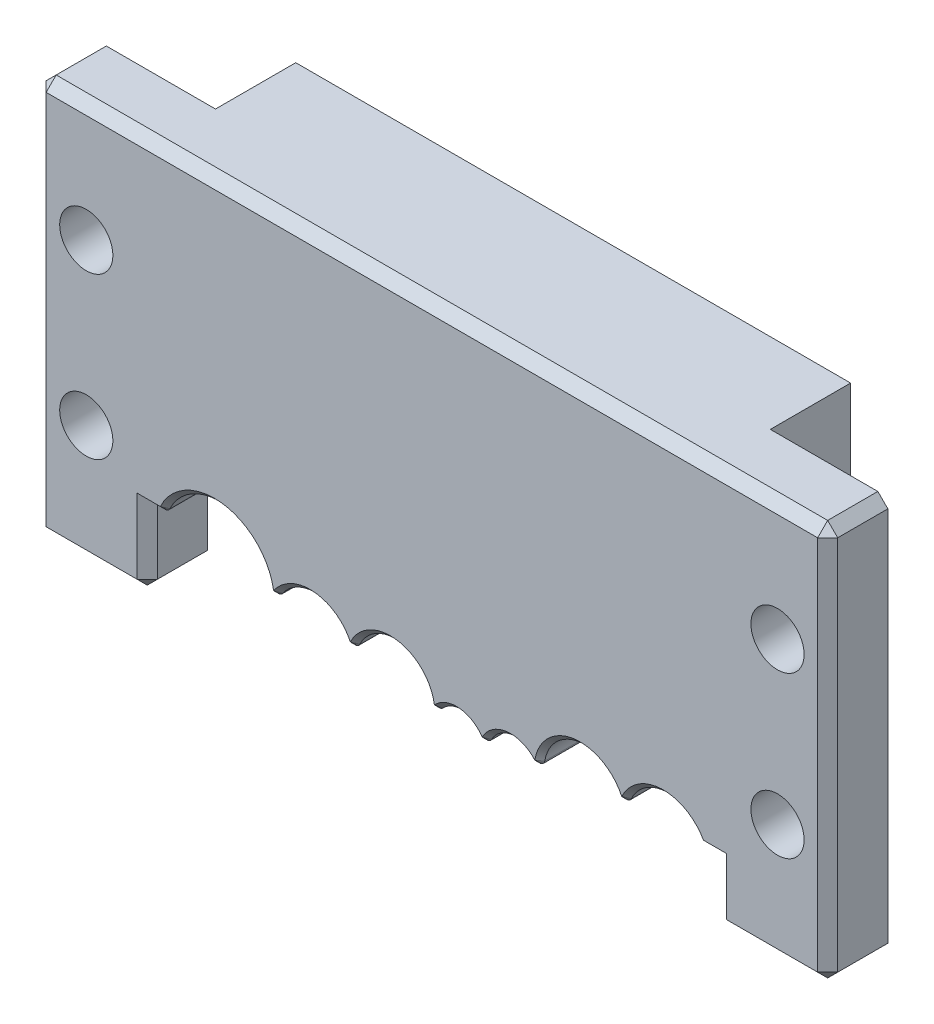
SolidWorks part; units mm, degrees
ref_plane "Front Plane" through (0, 0, 0) normal (0, 0, 1) x (1, 0, 0)
ref_plane "Top Plane" through (0, 0, 0) normal (0, 1, 0) x (1, 0, 0)
ref_plane "Right Plane" through (0, 0, 0) normal (1, 0, 0) x (0, 0, -1)
sketch "Sketch1" plane through (0, 0, 0) normal (0, 1, 0) x (1, 0, 0)
  point P0 (0, 0)
  line B0 (28.37, 45.6802) -> (28.37, 0) construction
  line B1 (28.37, 0) -> (39.45, 0) construction
  line B2 (39.45, 0) -> (39.45, 39.05) construction
  line B3 (39.45, 39.05) -> (36.7, 40.8) construction
  line B4 (36.7, 40.8) -> (36.7, 59.75) construction
  line B5 (36.7, 59.75) -> (32.77, 59.75) construction
  line B6 (32.77, 59.75) -> (32.77, 45.6802) construction
  line B7 (32.77, 45.6802) -> (28.37, 45.6802) construction
  line B8 (-28.37, 0) -> (-28.37, 45.6802) construction
  line B9 (-28.37, 45.6802) -> (-32.77, 45.6802) construction
  line B10 (-32.77, 45.6802) -> (-32.77, 59.75) construction
  line B11 (-32.77, 59.75) -> (-36.7, 59.75) construction
  line B12 (-36.7, 59.75) -> (-36.7, 40.8) construction
  line B13 (-36.7, 40.8) -> (-39.45, 39.05) construction
  line B14 (-39.45, 39.05) -> (-39.45, 0) construction
  line B15 (-39.45, 0) -> (-28.37, 0) construction
  line B16 (28.37, 0) -> (-28.37, 0) construction
  circle B17 centre (34.45, 9.5) radius 2.95 construction
  circle B18 centre (34.45, 25.5) radius 2.95 construction
  circle B19 centre (-34.45, 9.5) radius 2.95 construction
  circle B20 centre (-34.45, 25.5) radius 2.95 construction
sketch_block_instance "Block1-1"
sketch_block "Block1"
sketch "Sketch2" plane through (0, 0, 0) normal (0, 0, 1) x (1, 0, 0)
  line B0 (-39.5328, 0) -> (-39.5328, -39.5) construction
  line B1 (-39.5328, -39.5) -> (-28.4528, -39.5) construction
  line B2 (-28.4528, -39.5) -> (-28.4528, 0) construction
  line B3 (-28.4528, 0) -> (-39.5328, 0) construction
  line B4 (39.3672, -39.5) -> (39.3672, 0) construction
  line B5 (39.3672, 0) -> (28.2872, 0) construction
  line B6 (28.2872, 0) -> (28.2872, -39.5) construction
  line B7 (28.2872, -39.5) -> (39.3672, -39.5) construction
  circle B8 centre (-34.5328, -11.75) radius 2.95 construction
  circle B9 centre (34.3672, -11.75) radius 2.95 construction
  circle B10 centre (-34.5328, -27.75) radius 2.95 construction
  circle B11 centre (34.3672, -27.75) radius 2.95 construction
sketch_block_instance "Block2-1"
sketch_block "Block2"
ref_plane "Plane1" through (0, -39.5, 0) normal (0, 1, 0) x (1, 0, 0)
sketch "Sketch3" plane through (0, 0, 0) normal (0, 1, 0) x (1, 0, 0)
  line L0 (-39.45, 0) -> (-39.45, 32)
  line L1 (-39.45, 39.05) -> (-39.45, 0) construction
  line L2 (-39.45, 32) -> (39.45, 32)
  line L3 (39.45, 0) -> (39.45, 39.05) construction
  line L4 (39.45, 32) -> (39.45, 0)
  line L5 (39.45, 0) -> (-39.45, 0)
  circle A0 centre (-34.45, 9.5) radius 2.375
  circle A1 centre (34.45, 9.5) radius 2.375
  circle A2 centre (-34.45, 25.5) radius 2.375
  circle A3 centre (34.45, 25.5) radius 2.375
  dimension "D2" = 4.75
  dimension "D1" = 32
extrude "Boss-Extrude1" add sketch "Sketch3" along normal blind 10 contours L2 L4 L5 L0
extrude "Cut-Extrude1" cut sketch "Sketch3<4>" along normal blind 8 contours A0 | A1 | A2 | A3
sketch "Sketch3<4>" plane through (0, 0, 0) normal (0, 1, 0) x (1, 0, 0) same geometry as "Sketch3"
sketch "Sketch4" plane through (0, 0, 0) normal (0, 0, 1) x (1, 0, 0)
  line L0 (-39.5328, -39.5) -> (-28.4528, -39.5) construction
  line L2 (-27.6528, -39.5) -> (-27.6528, 0)
  line L3 (-27.6528, -39) -> (-27.6528, 0)
  line L4 (-27.6528, 0) -> (27.4872, 0)
  line L5 (27.4872, 0) -> (27.4872, -39.5)
  line L6 (27.4872, 0) -> (27.4872, -39)
  line L7 (-27.6528, -39) -> (27.4872, -39)
  dimension "D3" = 0.5
  dimension "D1" = 0.8
  dimension "D2" = 0.8
extrude "Boss-Extrude2" add sketch "Sketch4" against normal blind 6
sketch "Sketch6" plane through (0, 0, 0) normal (0, 0, 1) x (1, 0, 0)
  line L0 (-27.1328, -33.625) -> (-16.3828, -33.625) construction
  line L1 (-16.0328, -35.175) -> (-8.3828, -35.175) construction
  line L2 (-8.0328, -35.175) -> (-0.3828, -35.175) construction
  line L3 (-0.0328, -36.575) -> (4.8172, -36.575) construction
  line L4 (5.1672, -36.4) -> (10.3672, -36.4) construction
  line L5 (10.7172, -35.025) -> (18.6672, -35.025) construction
  line L6 (19.0172, -35.025) -> (26.9672, -35.025) construction
  line L7 (-27.6528, -39) -> (27.4872, -39) construction
  line L10 (-27.6528, -39) -> (27.4872, -39)
  line L11 (-27.1328, -33.625) -> (-27.6528, -33.625) construction
  line L12 (-27.6528, 0) -> (-27.6528, -39) construction
  line L13 (26.9672, -35.025) -> (27.4872, -35.025) construction
  line L14 (27.4872, -39) -> (27.4872, 0) construction
  line L23 (-27.6528, -39) -> (-27.6528, -31.057)
  line L24 (27.4872, -32.7955) -> (27.4872, -39)
  circle A0 centre (-21.7578, -33.625) radius 5.375 construction
  circle A1 centre (-12.2078, -35.175) radius 3.825 construction
  circle A2 centre (-4.2078, -35.175) radius 3.825 construction
  circle A3 centre (2.3922, -36.575) radius 2.425 construction
  circle A4 centre (7.7672, -36.4) radius 2.6 construction
  circle A5 centre (14.6922, -35.025) radius 3.975 construction
  circle A6 centre (22.9922, -35.025) radius 3.975 construction
  arc A7 (-16.3524, -32.7544) -> (-26.7013, -31.2719) centre (-21.7578, -33.625) ccw
  arc A8 (-8.6597, -33.4966) -> (-15.4462, -32.9574) centre (-12.2078, -35.175) ccw
  arc A9 (-0.3255, -34.5973) -> (-7.7558, -33.4966) centre (-4.2078, -35.175) ccw
  arc A10 (4.5085, -35.1976) -> (0.5365, -34.8627) centre (2.3922, -36.575) ccw
  arc A11 (9.7997, -34.6226) -> (5.3712, -35.1554) centre (7.7672, -36.4) ccw
  arc A12 (18.3887, -33.3098) -> (10.6697, -34.3734) centre (14.6922, -35.025) ccw
  arc A13 (26.5506, -33.0392) -> (19.2958, -33.3098) centre (22.9922, -35.025) ccw
  circle A14 centre (-21.7578, -33.625) radius 5.475 construction
  circle A15 centre (-12.2078, -35.175) radius 3.925 construction
  circle A16 centre (-4.2078, -35.175) radius 3.925 construction
  circle A17 centre (2.3922, -36.575) radius 2.525 construction
  circle A18 centre (7.7672, -36.4) radius 2.7 construction
  circle A19 centre (14.6922, -35.025) radius 4.075 construction
  circle A20 centre (22.9922, -35.025) radius 4.075 construction
  arc A21 (-16.3524, -32.7544) -> (-15.4462, -32.9574) centre (-15.8588, -32.6749) ccw
  arc A22 (-8.6597, -33.4966) -> (-7.7558, -33.4966) centre (-8.2078, -33.2827) ccw
  arc A23 (-0.3255, -34.5973) -> (0.5365, -34.8627) centre (0.169, -34.5237) ccw
  arc A24 (4.5085, -35.1976) -> (5.3712, -35.1554) centre (4.9275, -34.9249) ccw
  arc A25 (9.7997, -34.6226) -> (10.6697, -34.3734) centre (10.1761, -34.2935) ccw
  arc A26 (18.3887, -33.3098) -> (19.2958, -33.3098) centre (18.8422, -33.0994) ccw
  arc A27 (26.5506, -33.0392) -> (27.4872, -32.7955) centre (26.9872, -32.7955) ccw
  arc A28 (-27.6528, -31.057) -> (-26.7013, -31.2719) centre (-27.1528, -31.057) ccw
  dimension "D1" = 7.95
  dimension "D2" = 7.95
  dimension "D3" = 5.2
  dimension "D4" = 4.85
  dimension "D5" = 7.65
  dimension "D6" = 7.65
  dimension "D7" = 10.75
  dimension "D15" = 1
  dimension "D9" = 0.35
  dimension "D10" = 0.35
  dimension "D12" = 0.35
  dimension "D13" = 0.35
  dimension "D14" = 0.35
  dimension "D8" = 0.35
  dimension "D11" = 0.1
extrude "Cut-Extrude2" cut sketch "Sketch6" against normal up to next
sketch "Sketch9" plane through (0, 0, 0) normal (0, 0, 1) x (1, 0, 0)
  line L1 (-39.45, 10) -> (39.45, 10)
  line L2 (-39.45, 10) -> (-39.45, 0)
  line L3 (-39.45, 0) -> (39.45, 0)
  line L4 (39.45, 10) -> (39.45, 0)
  line L5 (0, 0) -> (0, 10) construction
  line L6 (-39.45, 5) -> (39.45, 5) construction
  point P168 (0, 5)
extrude "Cut-Extrude4" cut sketch "Sketch9" against normal through all
sketch "Sketch10" plane through (0, 0, -6) normal (0, 0, -1) x (-1, 0, 0)
  line L0 (-27.4872, -32.7955) -> (-27.4872, 0) construction
  line L5 (-27.4872, 0) -> (-39.3672, 0)
  line L6 (-39.3672, 0) -> (-39.3672, -39.5)
  line L7 (-39.3672, -39.5) -> (-28.2872, -39.5)
  line L8 (-28.2872, -39.5) -> (-28.2872, -33.2955)
  line L9 (-28.2872, 0) -> (-28.2872, -39.5) construction
  line L10 (-28.2872, -33.2955) -> (-26.9872, -33.2955)
  line L11 (-27.4872, -32.7955) -> (-27.4872, 0)
  line L12 (27.6528, 0) -> (39.5328, 0)
  line L13 (39.5328, 0) -> (39.5328, -39.5)
  line L14 (39.5328, -39.5) -> (28.4528, -39.5)
  line L15 (28.4528, -39.5) -> (28.4528, -31.557)
  line L16 (28.4528, -39.5) -> (28.4528, 0) construction
  line L17 (28.4528, -31.557) -> (27.1528, -31.557)
  line L18 (27.6528, 0) -> (27.6528, -31.057) construction
  line L19 (27.6528, 0) -> (27.6528, -31.057)
  arc A0 (-27.4872, -32.7955) -> (-26.9872, -33.2955) centre (-26.9872, -32.7955) ccw
  arc A1 (-27.4872, -32.7955) -> (-26.5506, -33.0392) centre (-26.9872, -32.7955) ccw construction
  arc A2 (26.7013, -31.2719) -> (27.6528, -31.057) centre (27.1528, -31.057) ccw construction
  arc A3 (27.1528, -31.557) -> (27.6528, -31.057) centre (27.1528, -31.057) ccw
  circle A4 centre (-34.3672, -11.75) radius 2.65
  circle A5 centre (-34.3672, -27.75) radius 2.65
  circle A6 centre (34.5328, -11.75) radius 2.65
  circle A7 centre (34.5328, -27.75) radius 2.65
  dimension "D1" = 5.3
extrude "Boss-Extrude4" add sketch "Sketch10" against normal up to surface (6 mm away) up to face at (1.115, -29.0541, 0)
sketch "Sketch11" plane through (0, 0, 0) normal (0, 0, 1) x (1, 0, 0)
  line L0 (-39.5328, 0) -> (39.3672, 0) construction
  line L1 (-27.6528, 0) -> (27.6528, 0)
  line L2 (-27.6528, 0) -> (-27.6528, -8)
  line L3 (-27.6528, -8) -> (27.6528, -8)
  line L4 (27.6528, 0) -> (27.6528, -8)
  line L5 (0, -8) -> (0, 0) construction
  line L6 (-27.6528, -4) -> (27.6528, -4) construction
  line L7 (-28.4528, -39.5) -> (-28.4528, 0) construction
  point P196 (0, -4)
  dimension "D1" = 0.8
  dimension "D2" = 8
extrude "Boss-Extrude5" add sketch "Sketch11" along normal blind 8
fillet "Fillet2" radius 5 1 edges at (0, -8, 0)
chamfer "Chamfer3" distance 1 angle 45 13 edges at (-39.5328, -19.75, -6) (-28.4528, -35.5285, -6) (-33.9928, -39.5, -6) (-39.5328, -39.5, -3) (-39.5328, 0, -3) (28.2872, -36.3978, -6) (33.8272, -39.5, -6) (39.3672, -39.5, -3) (39.3672, -19.75, -6) (-0.0828, 0, -6) (39.3672, 0, -3) (-28.4528, -39.5, -3) (28.2872, -39.5, -3)
chamfer "Chamfer4" distance 0.5 angle 45 34 edges at (-28.3028, -31.557, -6) (-26.8858, -31.4798, -6) (-20.9814, -28.2053, -6) (-15.9681, -33.1628, -6) (-11.8969, -31.2623, -6) (-8.2078, -33.7827, -6) (-3.6326, -31.2924, -6) (0.0219, -35.0015, -6) (2.6044, -34.0589, -6) (4.952, -35.4243, -6) (7.4448, -33.7193, -6) (10.3138, -34.7742, -6) (28.1372, -33.2955, -6) (14.136, -30.9881, -6) (26.7341, -33.2267, -6) (18.8422, -33.5994, -6) (22.8403, -30.9528, -6) (-27.8028, -31.557, 0) (-26.8858, -31.4798, 0) (-20.9814, -28.2053, 0) (-15.9681, -33.1628, 0) (-11.8969, -31.2623, 0) (-8.2078, -33.7827, 0) (-3.6326, -31.2924, 0) (0.0219, -35.0015, 0) (2.6044, -34.0589, 0) (4.952, -35.4243, 0) (7.4448, -33.7193, 0) (10.3138, -34.7742, 0) (27.6372, -33.2955, 0) (14.136, -30.9881, 0) (26.7341, -33.2267, 0) (18.8422, -33.5994, 0) (22.8403, -30.9528, 0)
mirror "Mirror1" about plane through (39.45, 10, 0) normal (0, 0, 1) of bodies 109
delete or keep bodies "Body-Delete/Keep 1" type delete bodies bodies 109
equation "\"D14@Sketch6\"=\"D9@Sketch6\""
equation "\"D10@Sketch6\"=\"D9@Sketch6\""
equation "\"D13@Sketch6\"=\"D9@Sketch6\""
equation "\"D12@Sketch6\"=\"D9@Sketch6\""
equation "\"D8@Sketch6\"=\"D9@Sketch6\""
